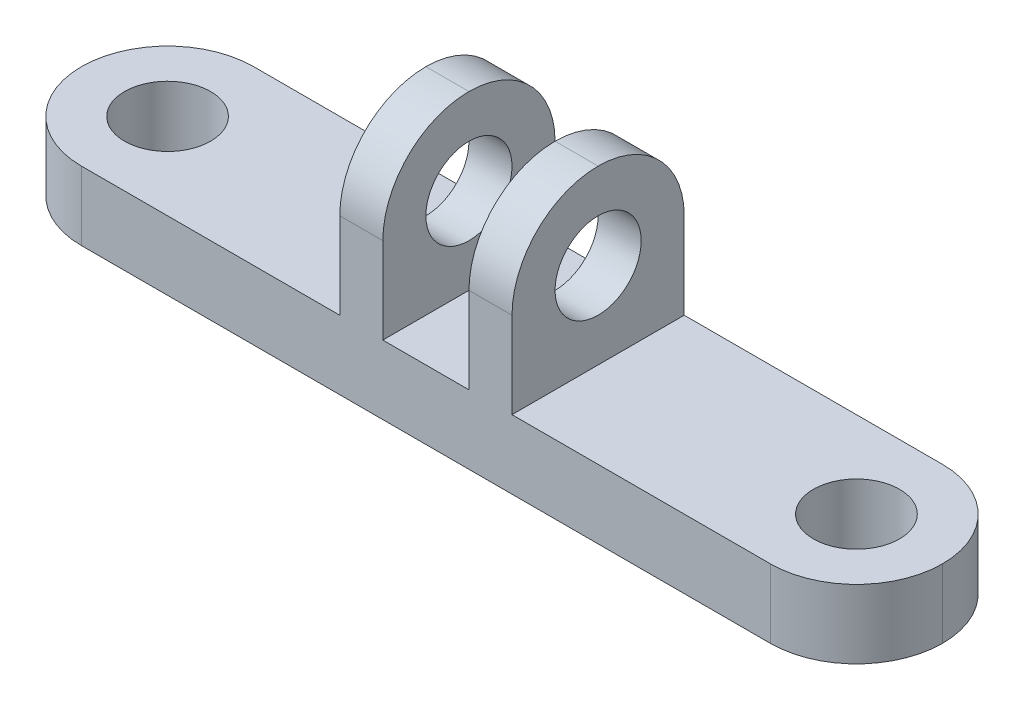
SolidWorks part; units mm, degrees
ref_plane "Front Plane" through (0, 0, 0) normal (0, 0, 1) x (1, 0, 0)
ref_plane "Top Plane" through (0, 0, 0) normal (0, 1, 0) x (1, 0, 0)
ref_plane "Right Plane" through (0, 0, 0) normal (1, 0, 0) x (0, 0, -1)
sketch "Sketch2" plane through (0, 0, 0) normal (0, 1, 0) x (1, 0, 0)
  line L0 (-12.7, 0) -> (12.7, 0) construction
  line L1 (-15.875, -3.175) -> (15.875, -3.175)
  line L2 (-15.875, -3.175) -> (-15.875, 3.175)
  line L3 (-15.875, 3.175) -> (15.875, 3.175)
  line L4 (15.875, -3.175) -> (15.875, 3.175)
  circle A0 centre (-12.7, 0) radius 1.5875
  circle A1 centre (12.7, 0) radius 1.5875
  point P4 (0, 3.175)
  point P6 (-15.875, 0)
  point P7 (12.6961, -0.3139)
  point P13 (0, 0)
  point P14 (0, 0)
  point P15 (0, 0)
  point P16 (0, 0)
  dimension "D3" = 3.175
  dimension "D1" = 6.35
  dimension "D2" = 31.75
  dimension "D4" = 25.4
extrude "Boss-Extrude1" add sketch "Sketch2" along normal blind 2.54
sketch "Sketch3" plane through (0, 2.54, 0) normal (0, 1, 0) x (1, 0, 0)
  line L0 (15.875, 3.175) -> (-15.875, 3.175) construction
  line L1 (-3.175, -3.175) -> (-1.5875, -3.175)
  line L2 (-3.175, -3.175) -> (-3.175, 3.175)
  line L3 (-3.175, 3.175) -> (-1.5875, 3.175)
  line L4 (-1.5875, -3.175) -> (-1.5875, 3.175)
  line L5 (-15.875, -3.175) -> (15.875, -3.175) construction
  line L6 (0, 0) -> (-2.3813, 0) construction
  line L7 (1.5875, -3.175) -> (3.175, -3.175)
  line L8 (1.5875, -3.175) -> (1.5875, 3.175)
  line L9 (1.5875, 3.175) -> (3.175, 3.175)
  line L10 (3.175, -3.175) -> (3.175, 3.175)
  line L11 (0, 0) -> (2.3813, 0) construction
  point P0 (0, 0)
  point P16 (1.84, 0)
  point P18 (2.3813, 3.175)
  point P19 (0, 0)
  point P20 (-2.3813, 3.175)
  dimension "D1" = 1.5875
  dimension "D2" = 6.35
extrude "Boss-Extrude2" add sketch "Sketch3" along normal blind 6.35
sketch "Sketch4" plane through (-1.5875, 0, 0) normal (1, 0, 0) x (0, 0, -1)
  line L0 (3.175, 8.89) -> (3.175, 2.54) construction
  line L1 (-3.175, 8.89) -> (3.175, 8.89) construction
  circle A0 centre (0, 5.715) radius 1.5875
  point P4 (3.175, 5.715)
  point P7 (0, 8.89)
  dimension "D1" = 3.175
extrude "Cut-Extrude1" cut sketch "Sketch4" against normal through all both and the other way through all
fillet "Fillet1" radius 3.175 8 edges at (-15.875, 1.27, 3.175) (-15.875, 1.27, -3.175) (15.875, 1.27, -3.175) (15.875, 1.27, 3.175) (2.3813, 8.89, 3.175) (2.3813, 8.89, -3.175) (-2.3812, 8.89, -3.175) (-2.3813, 8.89, 3.175)
